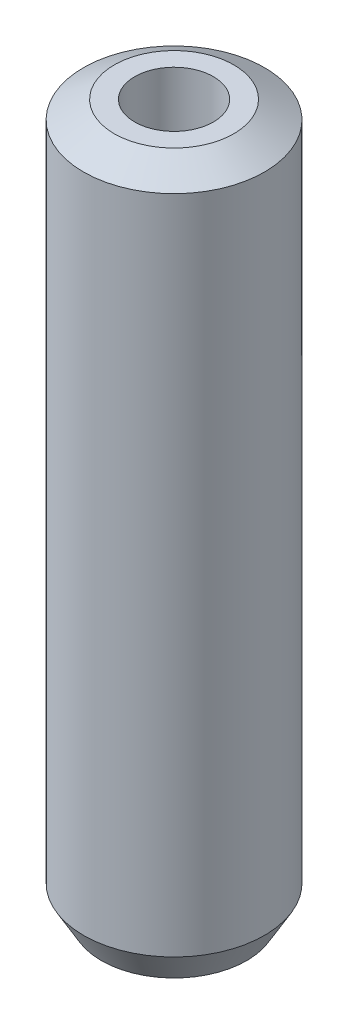
SolidWorks part; units mm, degrees
ref_plane "Front Plane" through (0, 0, 0) normal (0, 0, 1) x (1, 0, 0)
ref_plane "Top Plane" through (0, 0, 0) normal (0, 1, 0) x (1, 0, 0)
ref_plane "Right Plane" through (0, 0, 0) normal (1, 0, 0) x (0, 0, -1)
sketch "Sketch1" plane through (0, 0, 0) normal (0, 1, 0) x (1, 0, 0)
  circle A0 centre (0, 0) radius 20
  dimension "SHAFT_OD" = 40
extrude "Boss-Extrude1" add sketch "Sketch1" along normal blind 156.848
sketch "Sketch2" plane through (0, 0, 0) normal (0, 1, 0) x (1, 0, 0)
  circle A0 centre (0, 0) radius 8.6948
  dimension "BORE_D" = 17.3896
extrude "Cut-Extrude1" cut sketch "Sketch2" along normal through all
chamfer "Chamfer1" distance 3.9236 angle 60 2 edges at (0, 156.848, 20) (0, 0, 20) first distance on face at (0, 156.848, 20) first distance on face at (0, 0, 8.6948)
